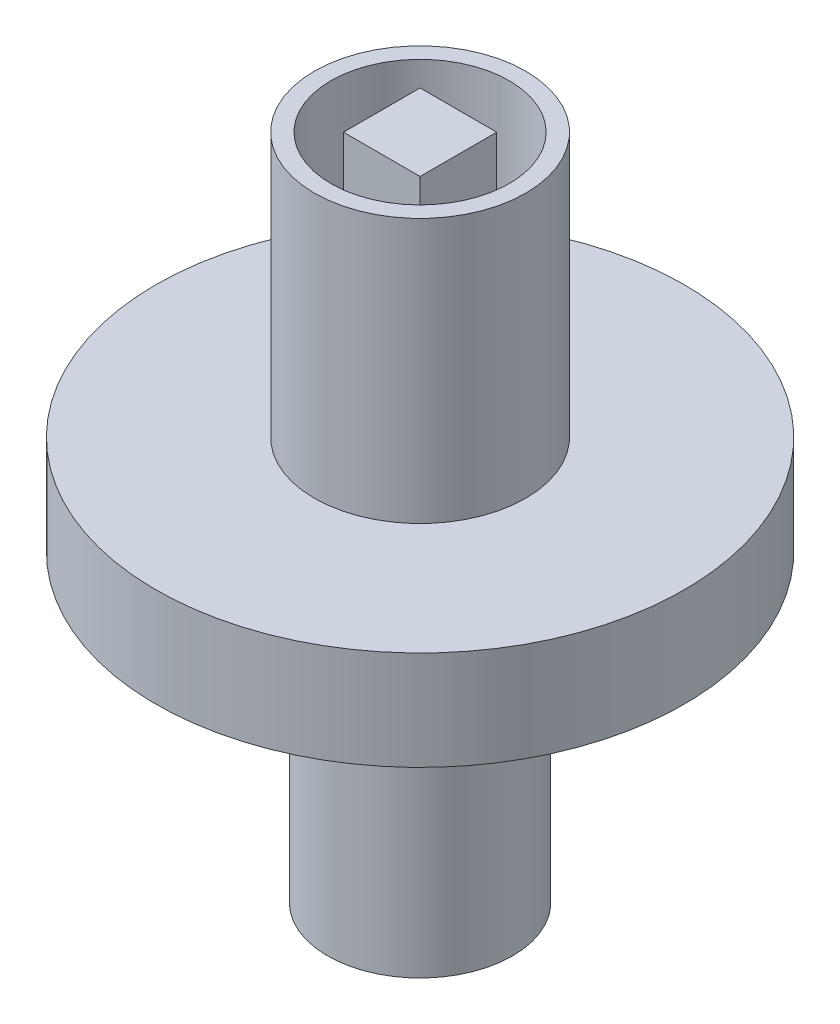
SolidWorks part; units mm, degrees
material "ABS"
ref_plane "Front Plane" through (0, 0, 0) normal (0, 0, 1) x (1, 0, 0)
ref_plane "Top Plane" through (0, 0, 0) normal (0, 1, 0) x (1, 0, 0)
ref_plane "Right Plane" through (0, 0, 0) normal (1, 0, 0) x (0, 0, -1)
sketch "Sketch1" plane through (0, 0, 0) normal (0, 0, 1) x (1, 0, 0)
  line L0 (0, 96.2797) -> (0, -99.3784) construction
  line L1 (-49.1359, 0) -> (108.8957, 0) construction
sketch "Sketch2" plane through (0, 0, 0) normal (0, 0, 1) x (1, 0, 0)
  line L0 (-49.1359, 0) -> (108.8957, 0) construction
  line L1 (20, 0) -> (20, 7.5)
  line L2 (20, 7.5) -> (8, 7.5)
  line L3 (8, 7.5) -> (8, 27.5)
  line L4 (8, 27.5) -> (0, 27.5)
  line L5 (0, 96.2797) -> (0, -99.3784) construction
  line L6 (0, 27.5) -> (0, 0)
  line L7 (0, 0) -> (20, 0)
  dimension "D1" = 20
  dimension "D2" = 8
  dimension "D3" = 7.5
  dimension "D4" = 20
revolve "Revolve2" add sketch "Sketch2" angle 360 about L0
sketch "Sketch3" plane through (0, 27.5, 0) normal (0, 1, 0) x (1, 0, 0)
  circle A0 centre (0, 0) radius 6.75
  dimension "D1" = 13.5
extrude "Cut-Extrude1" cut sketch "Sketch3" against normal blind 15 contours A0
sketch "Sketch4" plane through (0, 12.5, 0) normal (0, 1, 0) x (1, 0, 0)
  line L1 (-2.8952, 2.8974) -> (2.9048, 2.8974)
  line L2 (-2.8952, 2.8974) -> (-2.8952, -2.9026)
  line L3 (-2.8952, -2.9026) -> (2.9048, -2.9026)
  line L4 (2.9048, 2.8974) -> (2.9048, -2.9026)
  point P6 (0.0048, -0.0026)
extrude "Boss-Extrude1" add sketch "Sketch4" along normal blind 15
sketch "Sketch6" plane through (0, 0, 0) normal (0, -1, 0) x (1, 0, 0)
  circle A0 centre (0, 0) radius 7
  dimension "D1" = 14
extrude "Boss-Extrude2" add sketch "Sketch6" along normal blind 23
sketch "Sketch7" plane through (0, -23, 0) normal (0, -1, 0) x (1, 0, 0)
  circle A0 centre (0, 0) radius 3.5
  dimension "D1" = 7
extrude "Cut-Extrude2" cut sketch "Sketch7" against normal blind 15
sketch "Sketch8" plane through (0, -23, 0) normal (0, -1, 0) x (1, 0, 0)
  line L4 (-5.3, 1.5) -> (-1.5, 1.5)
  line L5 (-5.3, 1.5) -> (-5.3, -1.5)
  line L6 (5.3, 1.5) -> (5.3, -1.5)
  line L7 (-5.3, -1.5) -> (-1.5, -1.5)
  line L8 (-1.5, -5.3) -> (-1.5, -1.5)
  line L9 (-1.5, -5.3) -> (1.5, -5.3)
  line L10 (-1.5, 5.3) -> (1.5, 5.3)
  line L11 (1.5, -5.3) -> (1.5, -1.5)
  line L12 (1.5, 1.5) -> (5.3, 1.5)
  line L13 (1.5, 1.5) -> (1.5, 5.3)
  line L14 (1.5, -1.5) -> (5.3, -1.5)
  line L15 (-1.5, 1.5) -> (-1.5, 5.3)
  point P1 (0, 0)
  point P2 (0, 0)
  point P3 (0, 0)
  dimension "D1" = 10.6
  dimension "D2" = 3
  dimension "D3" = 10.6
  dimension "D4" = 3
extrude "Cut-Extrude3" cut sketch "Sketch8" against normal blind 15
equation "\"D1@Sketch2\"=40/2"
